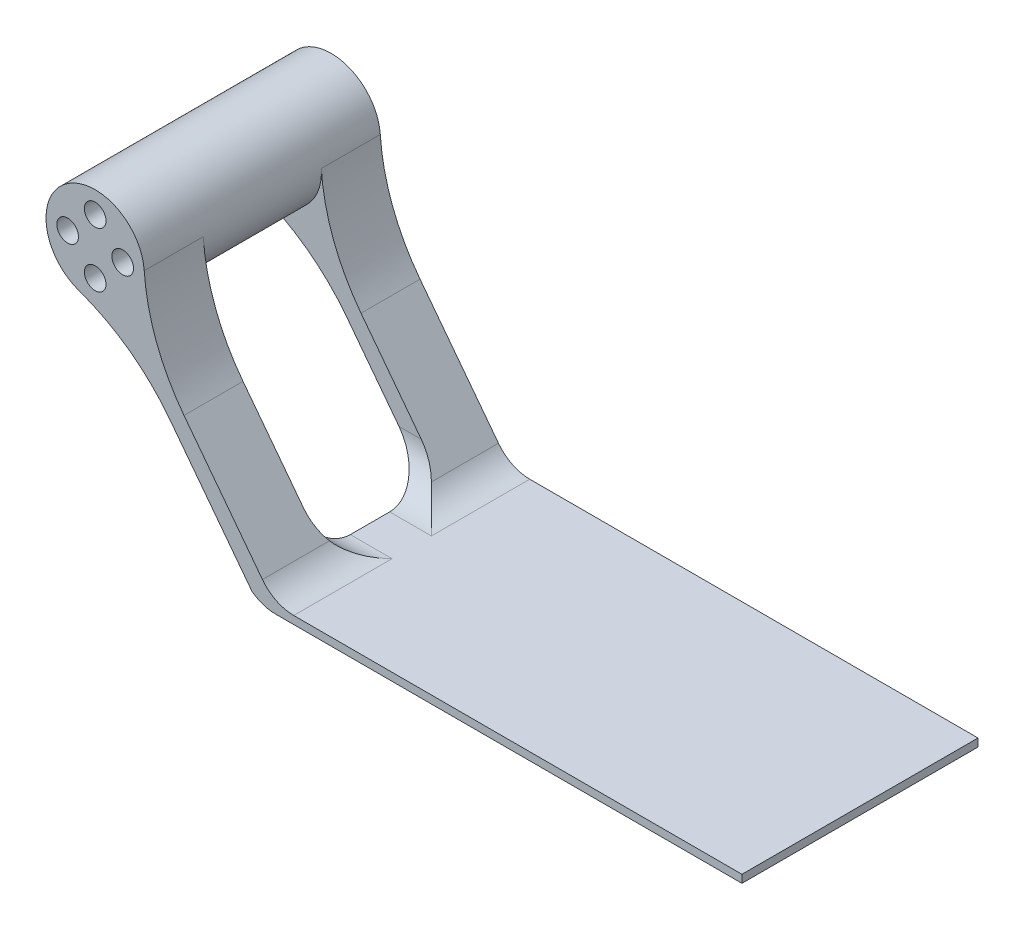
SolidWorks part; units mm, degrees
material "ABS"
ref_plane "Front" through (0, 0, 0) normal (0, 0, 1) x (1, 0, 0)
ref_plane "Top" through (0, 0, 0) normal (0, 1, 0) x (1, 0, 0)
ref_plane "Right" through (0, 0, 0) normal (1, 0, 0) x (0, 0, -1)
sketch "Sketch30" plane through (0, 0, 0) normal (0, 1, 0) x (1, 0, 0)
  line L3 (-70.6823, 10.08) -> (-70.6823, 34)
  line L4 (-70.6823, 34) -> (53.8677, 34)
  line L5 (53.8677, 34) -> (53.8677, -26)
  line L6 (53.8677, -26) -> (-70.6823, -26)
  line L7 (-70.6823, -26) -> (-70.6823, -8.5206)
  line L8 (-70.6823, -8.5206) -> (-70.6823, 10.08)
  dimension "D1" = 60
  dimension "D2" = 124.55
extrude "Boss-Extrude13" add sketch "Sketch30" along normal blind 2
fillet "Fillet1" radius 10 1 edges at (-70.6823, 0, -4)
sketch "Sketch31" plane through (0, 0, 26) normal (0, 0, 1) x (1, 0, 0)
  line L0 (-70.6823, 2) -> (-106.8719, 49.4885)
  line L1 (-106.8719, 49.4885) -> (-103.2928, 52.2161)
  line L2 (-103.2928, 52.2161) -> (-65.0245, 2)
  line L3 (-70.6823, 2) -> (53.8677, 2) construction
  line L4 (-65.0245, 2) -> (-70.6823, 2) construction
  line L5 (-67.8534, 2) -> (-110.5375, 58.0106) construction
  line L7 (53.8677, 2) -> (-70.6823, 2)
  line L8 (-64.6823, 0) -> (53.8677, 0)
  line L9 (53.8677, 0) -> (53.8677, 2)
  line L10 (53.8677, 2) -> (-65.0245, 2)
  line L11 (-64.6823, 0) -> (53.8677, 0)
  line L12 (53.8677, 0) -> (53.8677, 2)
  circle A0 centre (-110.5375, 58.0106) radius 12.5
  arc A1 (-70.6823, 2) -> (-64.6823, 0) centre (-64.6823, 10) ccw
  arc A3 (-70.6823, 2) -> (-64.6823, 0) centre (-64.6823, 10) ccw
  circle A4 centre (-110.5375, 65.0106) radius 2.75
  circle A5 centre (-103.5375, 58.0106) radius 2.75
  circle A6 centre (-110.5375, 51.0106) radius 2.75
  circle A7 centre (-117.5375, 58.0106) radius 2.75
  point P23 (-114.3479, 63.0106)
  point P25 (-104.3479, 49.8885)
  line M3 (53.8677, 2) -> (-70.6823, 2)
  dimension "D5" = 5.5
  dimension "D6" = 25
  dimension "D8" = 9
  dimension "D9" = 7
  dimension "D1" = 52.69
  dimension "D2" = 4.5
  dimension "D3" = 47.4885
  dimension "D7" = 7
  dimension "D10" = 7
  dimension "D11" = 7
  dimension "D4" = 0
extrude "Boss-Extrude17" add sketch "Sketch31" against normal blind 15 contours L2 L1 L0 M3 | L2 A0 L0 L1 A7 A6 A5 A4 | L0 A0 L2 L1 region at (-85.405, 25.068, 26) region at (-110.8012, 58.3567, 26) region at (-104.0419, 49.4869, 26)
fillet "Fillet2" radius 10 2 edges at (-67.8534, 2, 11) (-65.0245, 2, 18.5)
sketch "Sketch40" plane through (0, 2, 0) normal (0, 1, 0) x (1, 0, 0)
  line L0 (53.8677, 4) -> (-70.6823, 4) construction
  line L1 (53.8677, -26) -> (53.8677, 34) construction
  line L2 (-70.6823, 34) -> (-70.6823, -1) construction
ref_plane "Plane1" through (0, 0, -4) normal (0, 0, 1) x (1, 0, 0)
sketch "Sketch44" plane through (0, 0, 11) normal (0, 0, -1) x (-1, 0, 0)
  circle A0 centre (110.5375, 58.0106) radius 12.5
  circle A1 centre (103.5375, 58.0106) radius 2.75
  circle A2 centre (110.5375, 65.0106) radius 2.75
  circle A3 centre (110.5375, 51.0106) radius 2.75
  circle A4 centre (117.5375, 58.0106) radius 2.75
extrude "Boss-Extrude23" add sketch "Sketch44" along normal up to surface (15 mm away) up to plane "Plane1"
mirror "Mirror4" about plane through (0, 0, -4) normal (0, 0, 1) of "Fillet2", "Boss-Extrude17"
sketch "Sketch45" plane through (0, 0, -4) normal (0, 0, -1) x (-1, 0, 0)
  circle A1 centre (117.5375, 58.0106) radius 2.75
  circle A2 centre (117.5375, 58.0106) radius 2.75
  circle A3 centre (110.5375, 51.0106) radius 2.75
  circle A4 centre (110.5375, 51.0106) radius 2.75
  circle A5 centre (110.5375, 65.0106) radius 2.75
  circle A6 centre (110.5375, 65.0106) radius 2.75
  circle A7 centre (103.5375, 58.0106) radius 2.75
  circle A8 centre (103.5375, 58.0106) radius 2.75
  circle A9 centre (110.5375, 58.0106) radius 12.5
  circle A10 centre (110.5375, 58.0106) radius 12.5
  circle M6 centre (117.5375, 58.0106) radius 2.75
  circle M7 centre (110.5375, 51.0106) radius 2.75
  circle M8 centre (110.5375, 65.0106) radius 2.75
  circle M9 centre (103.5375, 58.0106) radius 2.75
  circle M10 centre (110.5375, 58.0106) radius 12.5
  dimension "D1" = 0
  dimension "D2" = 0
  dimension "D3" = 0
  dimension "D4" = 0
  dimension "D5" = 0
extrude "Boss-Extrude24" add sketch "Sketch45" along normal up to next contours M10 M7 M9 M8 M6 region at (-110.5375, 58.0106, -4)
fillet "Fillet3" radius 50 4 edges at (-104.8742, 46.8671, 18.5) (-104.8742, 46.8671, -26.5) (-101.2951, 49.5947, -26.5) (-101.2951, 49.5947, 18.5)
ref_plane "Plane3" through (0, 0, -4) normal (0, 0, -1) x (-1, 0, 0)
